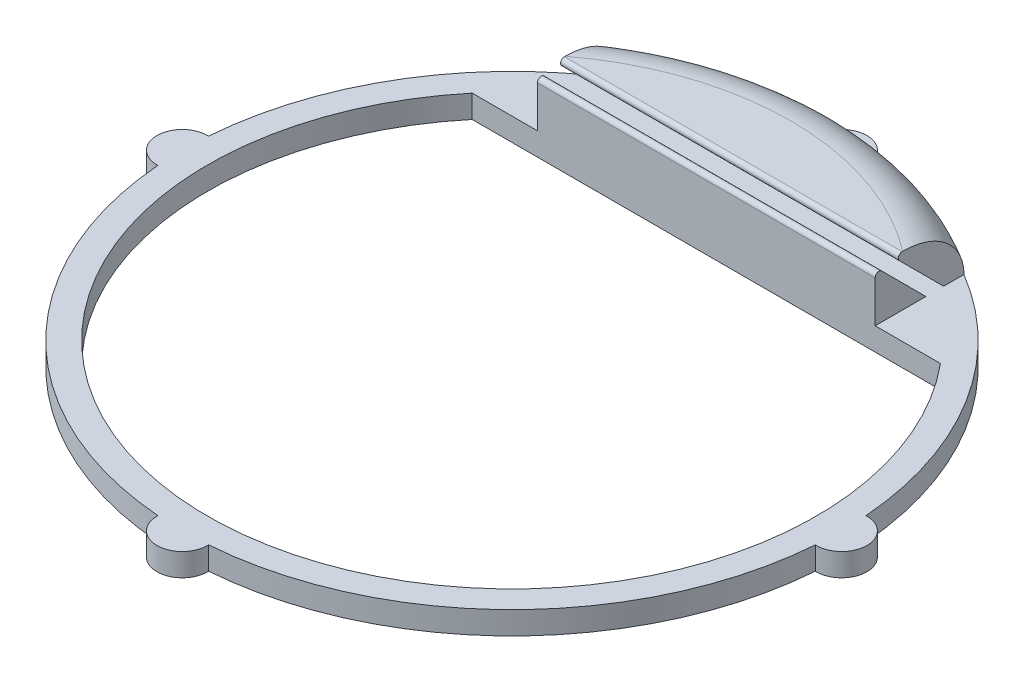
SolidWorks part; units mm, degrees
ref_plane "Front Plane" through (0, 0, 0) normal (0, 0, 1) x (1, 0, 0)
ref_plane "Top Plane" through (0, 0, 0) normal (0, 1, 0) x (1, 0, 0)
ref_plane "Right Plane" through (0, 0, 0) normal (1, 0, 0) x (0, 0, -1)
sketch "Sketch1" plane through (0, 0, 0) normal (0, 1, 0) x (1, 0, 0)
  line L0 (-21, 15.3297) -> (21, 15.3297) construction
  line L1 (-18.4662, 15.3297) -> (18.4662, 15.3297)
  arc A0 (-1.9985, 25.9231) -> (-25.9231, 1.9985) centre (0, 0) ccw
  arc A1 (1.9985, 25.9231) -> (-1.9985, 25.9231) centre (0, 26) ccw
  arc A2 (25.9231, -1.9985) -> (25.9231, 1.9985) centre (26, 0) ccw
  arc A3 (-1.9985, -25.9231) -> (1.9985, -25.9231) centre (0, -26) ccw
  arc A4 (-25.9231, 1.9985) -> (-25.9231, -1.9985) centre (-26, 0) ccw
  arc A5 (25.9231, 1.9985) -> (1.9985, 25.9231) centre (0, 0) ccw
  arc A6 (1.9985, -25.9231) -> (25.9231, -1.9985) centre (0, 0) ccw
  arc A7 (-25.9231, -1.9985) -> (-1.9985, -25.9231) centre (0, 0) ccw
  arc A8 (-18.4662, 15.3297) -> (18.4662, 15.3297) centre (0, 0) ccw
  point P14 (0, 0)
  dimension "D1" = 52
  dimension "D2" = 4
  dimension "D4" = 48
  dimension "D5" = 42
  dimension "D3" = 4
extrude "Boss-Extrude1" add sketch "Sketch1" along normal blind 1.8
sketch "Sketch2" plane through (0, 1.8, 0) normal (0, 1, 0) x (1, 0, 0)
  line L0 (-13.3186, 15.3297) -> (13.3186, 15.3297)
  line L1 (-13.3186, 15.3297) -> (-13.3186, 22.3297)
  line L2 (13.3186, 15.3297) -> (13.3186, 22.3297)
  arc A2 (13.3186, 22.3297) -> (-13.3186, 22.3297) centre (0, 0) ccw
  dimension "D1" = 90
  dimension "D2" = 7
  dimension "D3" = 90
  dimension "D4" = 7
extrude "Boss-Extrude3" add sketch "Sketch2" along normal blind 4
sketch "Sketch3" plane through (-13.3186, 0, 0) normal (-1, 0, 0) x (0, 0, 1)
  line L0 (-15.3297, 5.8) -> (-19.3297, 1.8)
  line L1 (-22.3297, 1.8) -> (-15.3297, 1.8) construction
  line L2 (-15.3297, 5.8) -> (-15.3297, 1.8) construction
  line L3 (-16.7297, 5.8) -> (-20.7297, 1.8)
  line L4 (-22.3297, 5.8) -> (-15.3297, 5.8) construction
  line L5 (-16.7297, 5.8) -> (-15.3297, 5.8)
  line L6 (-20.7297, 1.8) -> (-19.3297, 1.8)
  dimension "D1" = 45
  dimension "D2" = 45
  dimension "D3" = 1.4
extrude "Cut-Extrude1" cut sketch "Sketch3" against normal through all
fillet "Fillet1" radius 4 1 edges at (0, 5.8, -26)
fillet "Fillet2" radius 0.3 2 edges at (0, 5.8, -15.3297) (0, 5.8, -16.7297)
